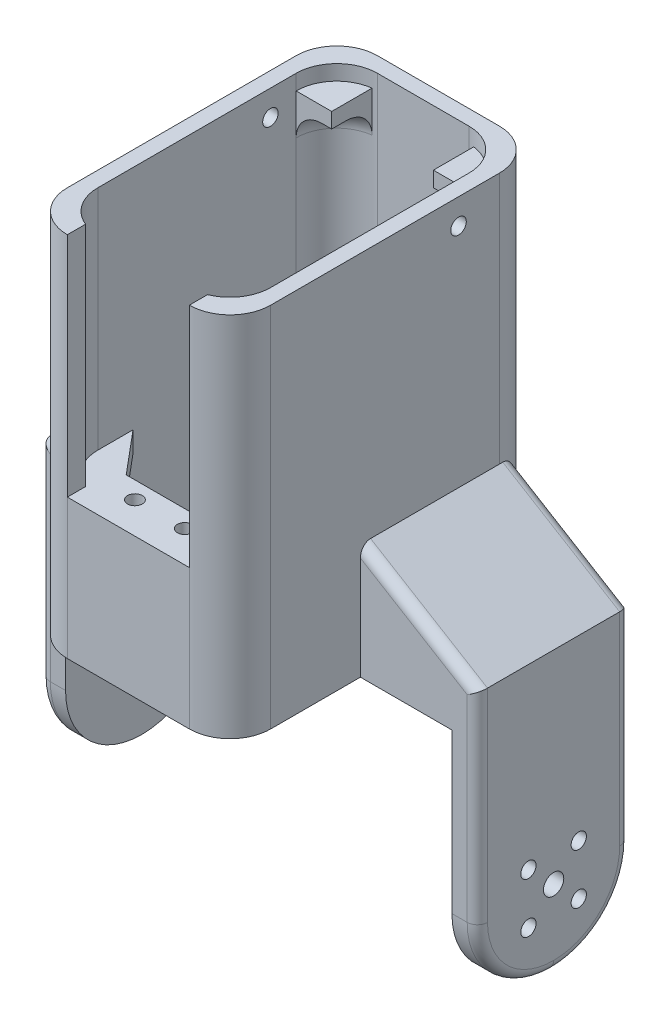
SolidWorks part; units mm, degrees
ref_plane "Front Plane" through (0, 0, 0) normal (0, 0, 1) x (1, 0, 0)
ref_plane "Top Plane" through (0, 0, 0) normal (0, 1, 0) x (1, 0, 0)
ref_plane "Right Plane" through (0, 0, 0) normal (1, 0, 0) x (0, 0, -1)
sketch "Sketch1" plane through (0, 0, 0) normal (0, 1, 0) x (1, 0, 0)
  line L0 (0, 61) -> (40, 0) construction
  line L1 (0, 0) -> (40, 0)
  line L2 (0, 0) -> (0, 61)
  line L3 (0, 61) -> (40, 61)
  line L4 (40, 0) -> (40, 61)
  line L5 (20, 30.5) -> (40, 61) construction
  line L7 (3, 3) -> (37, 3)
  line L8 (3, 3) -> (3, 58)
  line L9 (3, 58) -> (37, 58)
  line L10 (37, 3) -> (37, 58)
  line L11 (3, 3) -> (37, 58) construction
  line L12 (3, 58) -> (37, 3) construction
  dimension "D1" = 61
  dimension "D2" = 40
  dimension "D3" = 3
  dimension "D4" = 3
extrude "Boss-Extrude1" add sketch "Sketch1" along normal blind 72.2
fillet "Fillet1" radius 8 4 edges at (37, 36.1, -3) (3, 36.1, -3) (3, 36.1, -58) (37, 36.1, -58)
fillet "Fillet2" radius 8 4 edges at (0, 36.1, 0) (40, 36.1, 0) (40, 36.1, -61) (0, 36.1, -61)
ref_plane "Plane1" through (0, 27.5, 0) normal (0, -1, 0) x (-1, 0, 0)
sketch "Sketch2" plane through (0, 27.5, 0) normal (0, -1, 0) x (-1, 0, 0)
  line L0 (-11, 3) -> (-29, 3)
  line L1 (-3.127, 9.58) -> (-36.873, 9.58)
  line L4 (-15.1, 6.2) -> (-15.1, 54.8) construction
  line L5 (-20, 0) -> (-20, 6.2) construction
  line L6 (-8, 0) -> (-32, 0) construction
  line L7 (-20, 6.2) -> (-15.1, 6.2) construction
  line L8 (-20, 6.2) -> (-24.9, 6.2) construction
  line L9 (-11, 58) -> (-29, 58)
  line L11 (-36.873, 51.42) -> (-3.127, 51.42)
  line L12 (-15.1, 54.8) -> (-24.9, 54.8) construction
  line L14 (-32, 61) -> (-8, 61) construction
  line L15 (-20, 51.42) -> (-17.9948, 51.42)
  line L20 (-17.9948, 51.42) -> (-17.9948, 57.2237)
  line L21 (-17.9948, 57.2237) -> (-22.1353, 57.2237)
  line L22 (-22.1353, 57.2237) -> (-22.1353, 51.42)
  line L23 (-22.1353, 51.42) -> (-20, 51.42)
  line L24 (-24.9, 54.8) -> (-24.9, 6.2) construction
  arc A0 (-11, 3) -> (-3.127, 9.58) centre (-11, 11) ccw
  arc A1 (-29, 3) -> (-36.873, 9.58) centre (-29, 11) cw
  circle A3 centre (-15.1, 6.2) radius 1.45
  circle A4 centre (-24.9, 6.2) radius 1.45
  arc A5 (-3.127, 51.42) -> (-11, 58) centre (-11, 50) ccw
  arc A6 (-29, 58) -> (-36.873, 51.42) centre (-29, 50) ccw
  circle A8 centre (-15.1, 54.8) radius 1.45
  circle A9 centre (-24.9, 54.8) radius 1.45
  dimension "D3" = 2.9
  dimension "D5" = 2.9
  dimension "D1" = 6.58
  dimension "D2" = 9.8
  dimension "D4" = 9.58
  dimension "D6" = 6.2
  dimension "D7" = 3.2
extrude "Boss-Extrude2" add sketch "Sketch2" along normal blind 4 contours L9 A6 L11 L22 L21 L20 A5 A9 A8 | A1 L0 A0 L1 A4 A3 region at (20, 27.5, -6.5243) region at (6.0902, 27.5, -55.8746)
ref_plane "Plane8" through (0, 0, -30.5) normal (0, 0, -1) x (-1, 0, 0)
sketch "Sketch3" plane through (0, 0, 0) normal (0, 0, 1) x (1, 0, 0)
  line L0 (-33.55, 27.5) -> (33.55, 27.5) construction
  line L1 (8, 72.2) -> (32, 72.2)
  line L2 (8, 72.2) -> (8, 27.5)
  line L3 (8, 27.5) -> (32, 27.5)
  line L4 (32, 72.2) -> (32, 27.5)
extrude "Cut-Extrude1" cut sketch "Sketch3" against normal blind 4
ref_plane "Plane2" through (0, 0, -55.65) normal (0, 0, -1) x (-1, 0, 0)
sketch "Sketch5" plane through (0, 0, -55.65) normal (0, 0, -1) x (-1, 0, 0)
  line L0 (-40, 22.6231) -> (-63, 8.6446)
  line L1 (-40, 72.2) -> (-40, 0) construction
  line L2 (-63, 8.6446) -> (-63, -46.2661)
  line L3 (-63, -46.2661) -> (-58, -46.2661)
  line L4 (-58, -46.2661) -> (-58, 0)
  line L5 (-58, 0) -> (-40, 0)
  line L6 (-20, 0) -> (-20, -25.4294) construction
  line L7 (-8, 0) -> (-32, 0) construction
  line L8 (-40, 22.6231) -> (-40, 0)
  line L9 (0, 22.6231) -> (0, 0)
  line L10 (18, 0) -> (0, 0)
  line L11 (18, -46.2661) -> (18, 0)
  line L12 (23, -46.2661) -> (18, -46.2661)
  line L13 (23, 8.6446) -> (23, -46.2661)
  line L14 (0, 22.6231) -> (23, 8.6446)
  dimension "D1" = 5
  dimension "D2" = 76
extrude "Boss-Extrude3" add sketch "Sketch5" against normal blind 30
fillet "Fillet3" radius 15 2 edges at (60.5, -46.2661, -55.65) (60.5, -46.2661, -25.65)
fillet "Fillet4" radius 15 2 edges at (-20.5, -46.2661, -25.65) (-20.5, -46.2661, -55.65)
sketch "Sketch6" plane through (63, 0, 0) normal (1, 0, 0) x (0, 0, -1)
  circle A0 centre (40.65, -31.2661) radius 2
  dimension "D1" = 4
extrude "Cut-Extrude2" cut sketch "Sketch6" against normal up to surface (5 mm away) up to face at (58, -23.0023, -40.65)
sketch "Sketch8" plane through (63, 0, -67) normal (-1, 0, 0) x (0, 0, 1)
  line L0 (26.35, -31.2661) -> (21.4003, -36.2158) construction
  line L1 (26.35, -31.2661) -> (31.2997, -36.2158) construction
  line L2 (31.2997, -26.3163) -> (26.35, -31.2661) construction
  line L3 (26.35, -31.2661) -> (21.4003, -26.3163) construction
  line L5 (26.35, -31.2661) -> (26.35, -26.8418) construction
  line L6 (26.35, -26.8418) -> (26.35, -31.2661) construction
  line L9 (26.35, -31.2661) -> (26.35, -37.862) construction
  circle A5 centre (31.2997, -26.3163) radius 1.505
  circle A6 centre (21.4003, -26.3163) radius 1.505
  circle A7 centre (21.4003, -36.2158) radius 1.505
  circle A8 centre (31.2997, -36.2158) radius 1.505
  dimension "D1" = 45
  dimension "D2" = 45
  dimension "D5" = 3.01
  dimension "D4" = 7
  dimension "D3" = 45
extrude "Cut-Extrude3" cut sketch "Sketch8" along normal up to surface (5 mm away) up to face at (58, -31.2661, -38.65)
ref_plane "Plane3" through (0, 32.5, 0) normal (0, -1, 0) x (-1, 0, 0)
sketch "Sketch10" [suppressed] plane through (0, 32.5, 0) normal (0, -1, 0) x (-1, 0, 0)
  arc A0 (-8, 3.5838) -> (-3, 11) centre (-11, 11) ccw
fillet "Fillet5" radius 2 12 edges at (63, -41.8727, -30.0434) (63, -41.8727, -51.2566) (-23, -41.8727, -51.2566) (-23, -41.8727, -30.0434) (51.5, 15.6339, -25.65) (63, -11.3107, -25.65) (63, -11.3107, -55.65) (51.5, 15.6339, -55.65) (-23, -11.3107, -55.65) (-11.5, 15.6339, -55.65) (-23, -11.3107, -25.65) (-11.5, 15.6339, -25.65)
ref_plane "Plane4" through (0, 69.2, 0) normal (0, 1, 0) x (1, 0, 0)
sketch "Sketch11" plane through (0, 69.2, 0) normal (0, 1, 0) x (1, 0, 0)
  line L0 (3, 50) -> (3, 58) construction
  line L1 (3, 54) -> (51.2963, 53.65) construction
  line L2 (63, 53.65) -> (40, 53.65) construction
  line L3 (3, 50) -> (10, 50)
  line L4 (11, 58) -> (29, 58) construction
  line L6 (20, 58) -> (20, 41.7843) construction
  line L9 (10, 50) -> (10, 57.9373)
  line L10 (37, 50) -> (30, 50)
  line L11 (30, 50) -> (30, 57.9373)
  arc A0 (3, 50) -> (11, 58) centre (11, 50) cw
  arc A6 (37, 50) -> (29, 58) centre (29, 50) ccw
  dimension "D1" = 7
ref_plane "Plane5" through (20, 0, 0) normal (1, 0, 0) x (0, 0, -1)
ref_axis "Axis1" through (20, 75.81, -58) along (0, -1, 0)
ref_point "Point1"
extrude "Boss-Extrude5" add sketch "Sketch11" against normal blind 3 contours A0 L3 L9 | L10 A6 L11 region at (7.0582, 69.2, -53.2832) region at (32.9418, 69.2, -53.2832)
fillet "Fillet7" radius 5 2 edges at (35, 66.2, -55.2915) (5, 66.2, -55.2915)
sketch "Sketch12" plane through (3, 0, 0) normal (1, 0, 0) x (0, 0, -1)
  line L0 (50, 69.2) -> (44.95, 69.2) construction
  line L1 (44.95, 69.2) -> (44.95, 67.2) construction
  circle A0 centre (44.95, 67.2) radius 1.525
  dimension "D3" = 3.05
  dimension "D1" = 2
  dimension "D2" = 5.05
extrude "Cut-Extrude4" cut sketch "Sketch12" against normal up to surface (3 mm away) up to face at (0, 30.0591, -28.648)
sketch "Sketch13" plane through (37, 0, 0) normal (-1, 0, 0) x (0, 0, 1)
  circle A0 centre (-44.95, 67.2) radius 1.525
extrude "Cut-Extrude5" cut sketch "Sketch13" against normal up to surface (3 mm away) up to face at (40, 30.0591, -28.648)
sketch "Sketch14" plane through (0, 23.5, 0) normal (0, -1, 0) x (1, 0, 0)
  line L0 (3, -17.9223) -> (10, -9.58)
  line L1 (3, -50) -> (3, -11) construction
  line L2 (3.127, -9.58) -> (36.873, -9.58) construction
  line L3 (37, -17.9223) -> (30, -9.58)
  line L4 (37, -11) -> (37, -50) construction
  line L5 (3, -17.9223) -> (3, -9.58)
  line L6 (3, -9.58) -> (10, -9.58)
  line L7 (30, -9.58) -> (37, -9.58)
  line L8 (37, -9.58) -> (37, -17.9223)
  dimension "D1" = 7
  dimension "D2" = 40
extrude "Boss-Extrude6" add sketch "Sketch14" against normal up to surface (4 mm away) up to face at (20, 27.5, -4.1788)
ref_axis "Axis2" through (20, -3.61, -30.5) along (0, 1, 0)
ref_axis "Axis3" through (0, 67.2, -44.95) along (1, 0, 0)
